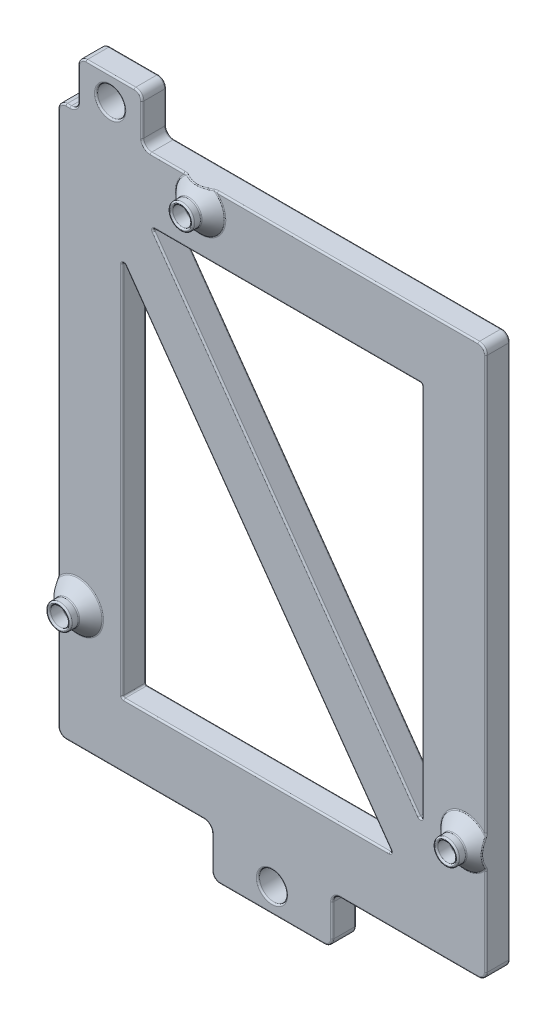
SolidWorks part; units mm, degrees
ref_plane "Ebene vorne" through (0, 0, 0) normal (0, 0, 1) x (1, 0, 0)
ref_plane "Ebene oben" through (0, 0, 0) normal (0, 1, 0) x (1, 0, 0)
ref_plane "Ebene rechts" through (0, 0, 0) normal (1, 0, 0) x (0, 0, -1)
sketch "Skizze1" plane through (0, 0, 0) normal (0, 0, 1) x (1, 0, 0)
  line L0 (8, 55.3987) -> (41.6605, 8)
  line L1 (0, 0) -> (19.17, 0)
  line L2 (0, 0) -> (0, 68.58)
  line L3 (0, 68.58) -> (2.5, 68.58)
  line L4 (53.34, 0) -> (53.34, 68.58)
  line L13 (41.6605, 8) -> (8, 8)
  line L14 (45.34, 13.1813) -> (45.34, 60.58)
  line L15 (45.34, 60.58) -> (11.6795, 60.58)
  line L16 (8, 8) -> (8, 55.3987)
  line L17 (45.5126, 7.7569) -> (8, 60.58) construction
  line L18 (45.34, 60.58) -> (8, 8) construction
  line L19 (11.6795, 60.58) -> (45.34, 13.1813)
  line L20 (34.17, 0) -> (53.34, 0)
  line L22 (34.17, 0) -> (34.17, -6)
  line L23 (34.17, -6) -> (19.17, -6)
  line L24 (19.17, 0) -> (19.17, -6)
  line L26 (2.5, 68.58) -> (2.5, 74.58)
  line L27 (2.5, 74.58) -> (10.5, 74.58)
  line L28 (10.5, 68.58) -> (10.5, 74.58)
  line L29 (10.5, 68.58) -> (53.34, 68.58)
  circle A0 centre (6.5, 71.58) radius 1.75
  circle A1 centre (26.67, -3) radius 1.75
  circle A2 centre (2.54, 15.24) radius 1.15
  circle A3 centre (50.8, 13.97) radius 1.15
  circle A4 centre (17.78, 66.04) radius 1.15
  point P11 (26.67, 34.29)
  point P24 (6.5, 74.58)
  point P26 (0, 34.29)
  point P27 (2.5, 71.58)
  point P39 (28.5098, 60.58)
  point P41 (8, 31.6994)
  point P46 (19.17, -3)
  point P47 (26.67, -6)
  dimension "D12" = 3.5
  dimension "D13" = 3.5
  dimension "D24" = 2.3
  dimension "D1" = 68.58
  dimension "D2" = 53.34
  dimension "D3" = 8
  dimension "D4" = 8
  dimension "D5" = 8
  dimension "D6" = 8
  dimension "D7" = 3
  dimension "D8" = 3
  dimension "D9" = 6
  dimension "D10" = 8
  dimension "D11" = 2.5
  dimension "D14" = 6
  dimension "D15" = 15
  dimension "D16" = 15.24
  dimension "D17" = 2.54
  dimension "D19" = 2.54
  dimension "D20" = 13.97
  dimension "D22" = 2.54
  dimension "D23" = 17.78
extrude "Aufsatz-Linear austragen1" add sketch "Skizze1" along normal blind 3
fillet "Verrundung2" radius 1 12 edges at (10.5, 68.58, 1.5) (10.5, 74.58, 1.5) (2.5, 74.58, 1.5) (2.5, 68.58, 1.5) (0, 68.58, 1.5) (0, 0, 1.5) (19.17, 0, 1.5) (19.17, -6, 1.5) (34.17, -6, 1.5) (34.17, 0, 1.5) (53.34, 0, 1.5) (53.34, 68.58, 1.5)
sketch "Skizze4" plane through (0, 0, 3) normal (0, 0, 1) x (1, 0, 0)
  circle A0 centre (17.78, 66.04) radius 1.55
  circle A1 centre (2.54, 15.24) radius 1.55
  circle A2 centre (50.8, 13.97) radius 1.55
  circle M33 centre (2.54, 15.24) radius 1.15
  circle M34 centre (50.8, 13.97) radius 1.15
  circle M35 centre (17.78, 66.04) radius 1.15
  dimension "D1" = 3.1
extrude "Aufsatz-Linear austragen3" add sketch "Skizze4" along normal blind 2.5 contours A1 M33 | A2 M34 | A0 M35 region at (16.2738, 66.04, 3) region at (1.0338, 15.24, 3) region at (49.2938, 13.97, 3)
chamfer "Fase2" distance 1.5 angle 45 3 edges at (16.23, 66.04, 3) (49.25, 13.97, 3) (0.99, 15.24, 3)
sketch "Skizze6" plane through (0, 0, 0) normal (0, 0, -1) x (-1, 0, 0)
  circle A0 centre (-50.8, 13.97) radius 1.85
  circle A1 centre (-17.78, 66.04) radius 1.85
  circle A2 centre (-2.54, 15.24) radius 1.85
  dimension "D1" = 3.7
extrude "Schnitt-Linear austragen3" cut sketch "Skizze6" against normal blind 3.7
fillet "Verrundung4" radius 0.2 97 edges at (0, 15.6175, 3.4821) (53.34, 13.5925, 3.4821) (18.1575, 68.58, 3.4821) (0.99, 15.24, 4.5) (49.25, 13.97, 4.5) (17.78, 62.99, 3) (47.75, 13.97, 3) (5.59, 15.24, 3) (16.23, 66.04, 4.5) (34.4629, -0.2929, 3) (34.4629, -0.2929, 0) (18.8771, -0.2929, 3) (18.8771, -0.2929, 0) (2.2071, 68.8729, 3) (2.2071, 68.8729, 0) (10.7929, 68.8729, 3) (10.7929, 68.8729, 0) (10.2071, 74.2871, 3) (2.7929, 74.2871, 3) (0.2929, 68.2871, 3) (0.2929, 0.2929, 3) (19.4629, -5.7071, 3) (33.8771, -5.7071, 3) (53.0471, 0.2929, 3) (53.0471, 68.2871, 3) (10.2071, 74.2871, 0) (2.7929, 74.2871, 0) (0.2929, 68.2871, 0) (0.2929, 0.2929, 0) (19.4629, -5.7071, 0) (33.8771, -5.7071, 0) (53.0471, 0.2929, 0) (53.0471, 68.2871, 0) (1.25, 68.58, 3) (2.5, 71.58, 3) (6.5, 74.58, 3) (10.5, 71.58, 3) (35.9042, 68.58, 3) (13.7958, 68.58, 3) (53.34, 6.6408, 3) (53.34, 41.6192, 3) (43.755, 0, 3) (34.17, -3, 3) (26.67, -6, 3) (19.17, -3, 3) (9.585, 0, 3) (0, 42.2542, 3) (0, 7.2758, 3) (1.25, 68.58, 0) (2.5, 71.58, 0) (6.5, 74.58, 0) (10.5, 71.58, 0) (31.92, 68.58, 0) (53.34, 34.29, 0) (43.755, 0, 0) (34.17, -3, 0) (26.67, -6, 0) (19.17, -3, 0) (9.585, 0, 0) (0, 34.29, 0) (8.25, 71.58, 3) (8.25, 71.58, 0) (11.6795, 60.58, 1.5) (45.34, 13.1813, 1.5) (45.34, 60.58, 1.5) (45.34, 36.8806, 3) (28.5098, 36.8806, 3) (28.5098, 60.58, 3) (45.34, 36.8806, 0) (28.5098, 36.8806, 0) (28.5098, 60.58, 0) (8, 8, 1.5) (41.6605, 8, 1.5) (8, 55.3987, 1.5) (24.8302, 31.6994, 3) (24.8302, 8, 3) (8, 31.6994, 3) (24.8302, 31.6994, 0) (24.8302, 8, 0) (8, 31.6994, 0) (28.42, -3, 3) (28.42, -3, 0) (4.09, 15.24, 5.5) (3.69, 15.24, 5.5) (52.35, 13.97, 5.5) (51.95, 13.97, 5.5) (19.33, 66.04, 5.5) (18.93, 66.04, 5.5) (1.39, 15.24, 3.7) (49.65, 13.97, 3.7) (16.63, 66.04, 3.7) (48.95, 13.97, 3.7) (48.95, 13.97, 0) (15.93, 66.04, 0) (15.93, 66.04, 3.7) (0.69, 15.24, 0) (0.69, 15.24, 3.7)
equation "\"D4@Skizze1\"=\"D3@Skizze1\""
equation "\"D5@Skizze1\"=\"D3@Skizze1\""
equation "\"D6@Skizze1\"=\"D3@Skizze1\""
equation "\"D8@Skizze1\"=\"D7@Skizze1\""
equation "\"D14@Skizze1\"=\"D9@Skizze1\""
